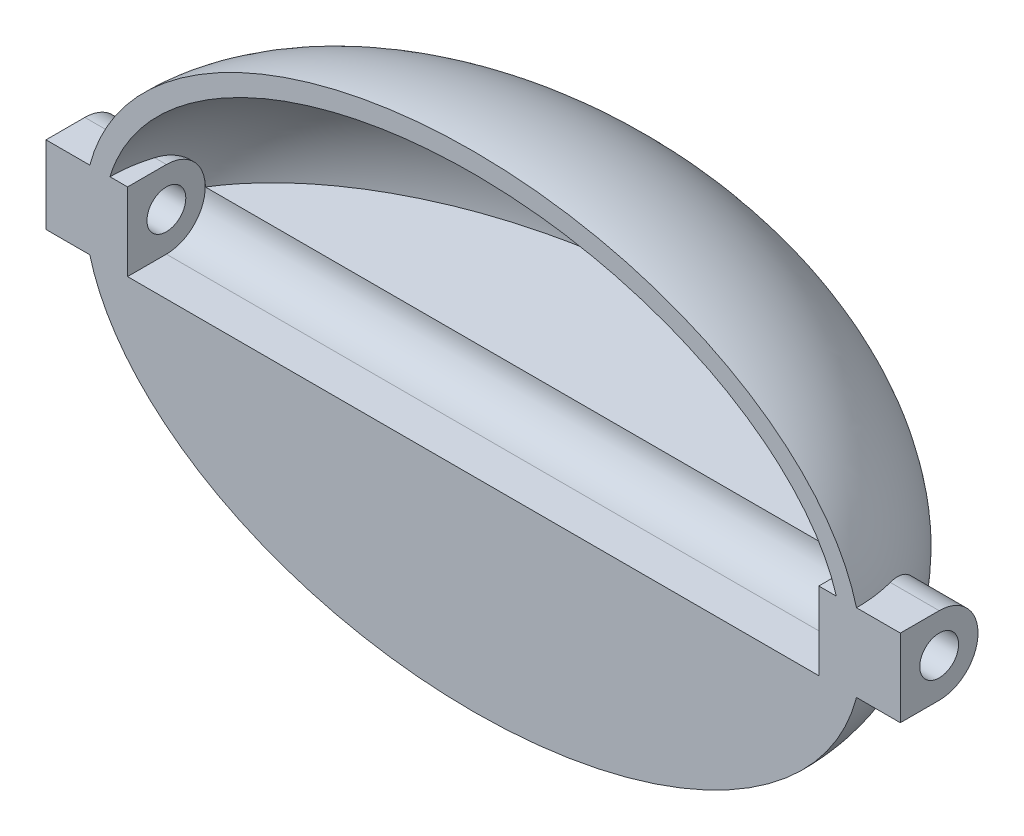
SolidWorks part; units mm, degrees
ref_plane "前视基准面" through (0, 0, 0) normal (0, 0, 1) x (1, 0, 0)
ref_plane "上视基准面" through (0, 0, 0) normal (0, 1, 0) x (1, 0, 0)
ref_plane "右视基准面" through (0, 0, 0) normal (1, 0, 0) x (0, 0, -1)
sketch "草图1" plane through (0, 0, 0) normal (0, 1, 0) x (1, 0, 0)
  line L0 (-376.7768, 0) -> (373.0191, 0) construction
  ellipse E0 centre (0, 0) end of major axis (200, 0) minor radius 125
  dimension "D1" = 250
  dimension "D2" = 400
revolve "旋转3" add sketch "草图1" angle 360 about L0
other "使用曲面切除1" flip cut yes
ref_plane "基准面1" through (0, -120, 0) normal (0, 1, 0) x (1, 0, 0)
sketch "草图2" plane through (0, -120, 0) normal (0, 1, 0) x (1, 0, 0)
  line L0 (-220.1966, 60) -> (220.5469, 60) construction
  line L1 (-137.5, 0) -> (137.5, 0) construction
  dimension "D1" = 60
ref_plane "基准面2" through (0, -125.2463, -45.5859) normal (0, 0.9397, 0.342) x (1, 0, 0)
sketch "草图3" plane through (0, -125.2463, -45.5859) normal (0, 0.9397, 0.342) x (1, 0, 0)
  line L0 (242.644, 40.5999) -> (-241.7114, 40.5999) construction
  line L1 (242.644, 63.6227) -> (-241.7114, 63.6227) construction
  line L2 (242.644, 23.6227) -> (-241.7114, 23.6227) construction
  line L3 (0, 214.3253) -> (0, -90.9867) construction
  line L4 (20, 214.3253) -> (20, -90.9867) construction
  line L5 (-20, 214.3253) -> (-20, -90.9867) construction
  line L6 (20, 63.6227) -> (-20, 63.6227)
  line L7 (-20, 63.6227) -> (-20, 23.6227)
  line L8 (-20, 23.6227) -> (20, 23.6227)
  line L9 (20, 23.6227) -> (20, 63.6227)
  dimension "D1" = 40
  dimension "D2" = 40
extrude "切除-拉伸1" cut sketch "草图3" along normal blind 70
sketch "草图4" plane through (0, 0, 0) normal (0, 0, 1) x (1, 0, 0)
  line L0 (-200, 0) -> (200, 0) construction
  line L1 (-189.2649, 10) -> (189.2649, 10)
  ellipse E1 centre (0, 0) end of major axis (200, 0) minor radius 125 (200, 0) -> (-200, 0) ccw construction
  ellipse E2 centre (0, 0) end of major axis (200, 0) minor radius 125 (200, 0) -> (-200, 0) ccw construction
  spline S0 degree 1 poles (189.2649, 10) (-189.2649, 10) knots 0 0 1 1 construction
  spline S1 degree 3 poles (189.2649, 10) (189.0166, 11.6856) (188.3998, 15.0246) (186.6607, 21.7177) (183.544, 30.0287) (178.2804, 39.8711) (169.2381, 52.6988) (154.19, 67.9384) (130.6173, 84.1337) (102.3316, 97.5039) (70.3463, 107.4698) (35.8196, 113.6157) (0, 115.6921) (-35.8196, 113.6157) (-70.3463, 107.4698) (-102.3316, 97.5039) (-130.6173, 84.1337) (-154.19, 67.9384) (-169.2381, 52.6988) (-178.2804, 39.8711) (-183.544, 30.0287) (-186.6607, 21.7177) (-188.3998, 15.0246) (-189.0166, 11.6856) (-189.2649, 10) knots 0.091785 0.091785 0.091785 0.091785 0.138004 0.184223 0.276661 0.369099 0.461538 0.646414 0.83129 1.016167 1.201043 1.38592 1.570796 1.755673 1.940549 2.125426 2.310302 2.495179 2.680055 2.772493 2.864932 2.95737 3.003589 3.049808 3.049808 3.049808 3.049808
  dimension "D1" = 10
revolve "切除-旋转1" cut sketch "草图4" angle 90 about L0 reverse direction yes
ref_plane "基准面3" through (220, 0, 0) normal (1, 0, 0) x (0, 0, -1)
sketch "草图5" plane through (220, 0, 0) normal (1, 0, 0) x (0, 0, -1)
  line L0 (-46.4571, 0) -> (160.9723, 0) construction
  line L1 (0, 20) -> (40, 20) construction
  line L2 (0, 137.5) -> (0, -137.5) construction
  line L3 (40, 20) -> (40, -20) construction
  line L4 (40, -20) -> (0, -20) construction
  line L5 (0, -20) -> (0, 20)
  line L6 (20, 20) -> (20, -20) construction
  line L7 (20, 20) -> (0, 20)
  line L8 (20, -20) -> (0, -20)
  line L9 (0, 20) -> (0, -20)
  arc A1 (20, 20) -> (20, -20) centre (20, 0) cw
  dimension "D1" = 40
  dimension "D2" = 40
extrude "切除-拉伸2" cut sketch "草图5" against normal through all contours A1 L7 L5 L8
sketch "草图6" plane through (220, 0, 0) normal (1, 0, 0) x (0, 0, -1)
  line L0 (20, -20) -> (0, -20) construction
  line L1 (20, 20) -> (0, 20) construction
  line L2 (0, -20) -> (0, 20) construction
  line L3 (20, -20) -> (0, -20)
  line L4 (20, 20) -> (0, 20)
  line L5 (0, -20) -> (0, 20)
  arc A0 (20, -20) -> (20, 20) centre (20, 0) ccw construction
  arc A1 (20, -20) -> (20, 20) centre (20, 0) ccw
extrude "凸台-拉伸1" add sketch "草图6" against normal blind 42
mirror "镜向1" about plane through (0, 0, 0) normal (1, 0, 0) of "凸台-拉伸1"
sketch "草图7" plane through (220, 0, 0) normal (1, 0, 0) x (0, 0, -1)
  circle A0 centre (20, 0) radius 10
  dimension "D1" = 20
extrude "切除-拉伸3" cut sketch "草图7" against normal blind 440
